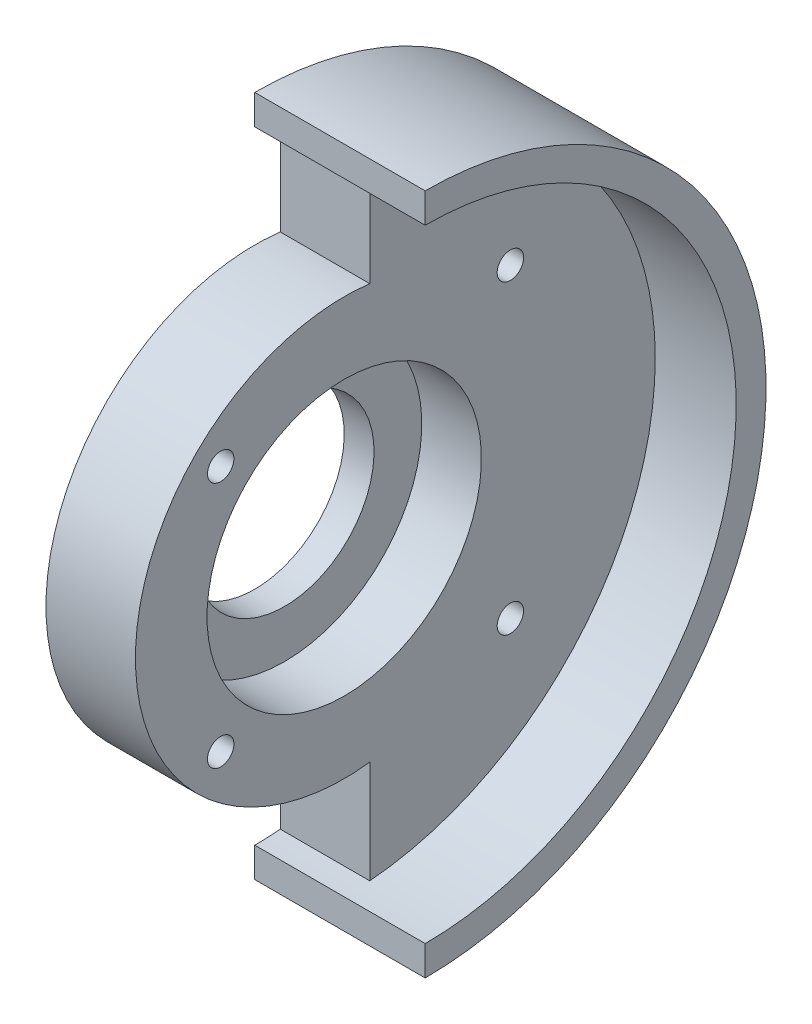
SolidWorks part; units mm, degrees
material "PLA 3D print"
ref_plane "Front Plane" through (0, 0, 0) normal (0, 0, 1) x (1, 0, 0)
ref_plane "Top Plane" through (0, 0, 0) normal (0, 1, 0) x (1, 0, 0)
ref_plane "Right Plane" through (0, 0, 0) normal (1, 0, 0) x (0, 0, -1)
sketch "Sketch1" plane through (0, 0, 0) normal (0, 0, 1) x (1, 0, 0)
  line L0 (20, 40) -> (20, 36.5)
  line L1 (20, 36.5) -> (10.5, 36.5)
  line L2 (10.5, 36.5) -> (10.5, 16.1)
  line L3 (10.5, 16.1) -> (3.5, 16.1)
  line L4 (3.5, 16.1) -> (3.5, 10.5)
  line L5 (3.5, 10.5) -> (0, 10.5)
  line L6 (0, 10.5) -> (0, 40)
  line L7 (0, 40) -> (20, 40)
  line L8 (20, 0) -> (0, 0) construction
  dimension "D1" = 20
  dimension "D2" = 7
  dimension "D3" = 9.5
  dimension "D4" = 10.5
  dimension "D5" = 16.1
  dimension "D6" = 36.5
  dimension "D7" = 40
revolve "Revolve1" add sketch "Sketch1" angle 360 about L8
sketch "Sketch2" plane through (10.5, 0, 0) normal (1, 0, 0) x (0, 0, -1)
  line L0 (3, 24.3156) -> (3, 36.3765)
  line L1 (3, -24.3156) -> (3, -36.3765)
  line L2 (0, 40) -> (0, 36.5)
  line L3 (0, -36.5) -> (0, -40)
  arc A0 (3, 36.3765) -> (0, 36.5) centre (0, 0) ccw
  arc A1 (3, 24.3156) -> (3, -24.3156) centre (0, 0) ccw
  circle A2 centre (-14.4957, 14.4957) radius 1.55
  circle A3 centre (0, 0) radius 36.5 construction
  arc A4 (3, 24.3156) -> (3, -24.3156) centre (0, 0) ccw construction
  circle A5 centre (19.5, -17.9444) radius 1.55
  circle A6 centre (19.5, 17.9444) radius 1.55
  circle A7 centre (19.5, 17.9444) radius 1.55 construction
  circle A9 centre (19.5, -17.9444) radius 1.55 construction
  arc A10 (0, 40) -> (0, -40) centre (0, 0) ccw
  circle A11 centre (0, 0) radius 40 construction
  arc A12 (0, -36.5) -> (3, -36.3765) centre (0, 0) ccw
  circle A13 centre (-14.4957, 14.4957) radius 1.55 construction
  circle A14 centre (-14.4957, -14.4957) radius 1.55
  circle A15 centre (-14.4957, -14.4957) radius 1.55 construction
extrude "Cut-Extrude1" cut sketch "Sketch2" against normal through all both and the other way through all
sketch "Sketch3" plane through (0, 0, 0) normal (-1, 0, 0) x (0, 0, 1)
  circle A0 centre (-19.5, 17.9444) radius 2.95
  circle A1 centre (14.4957, 14.4957) radius 2.95
  circle A2 centre (-19.5, -17.9444) radius 2.95
  circle A3 centre (14.4957, -14.4957) radius 2.95
  dimension "D1" = 5.9
extrude "Cut-Extrude2" cut sketch "Sketch3" against normal blind 5
